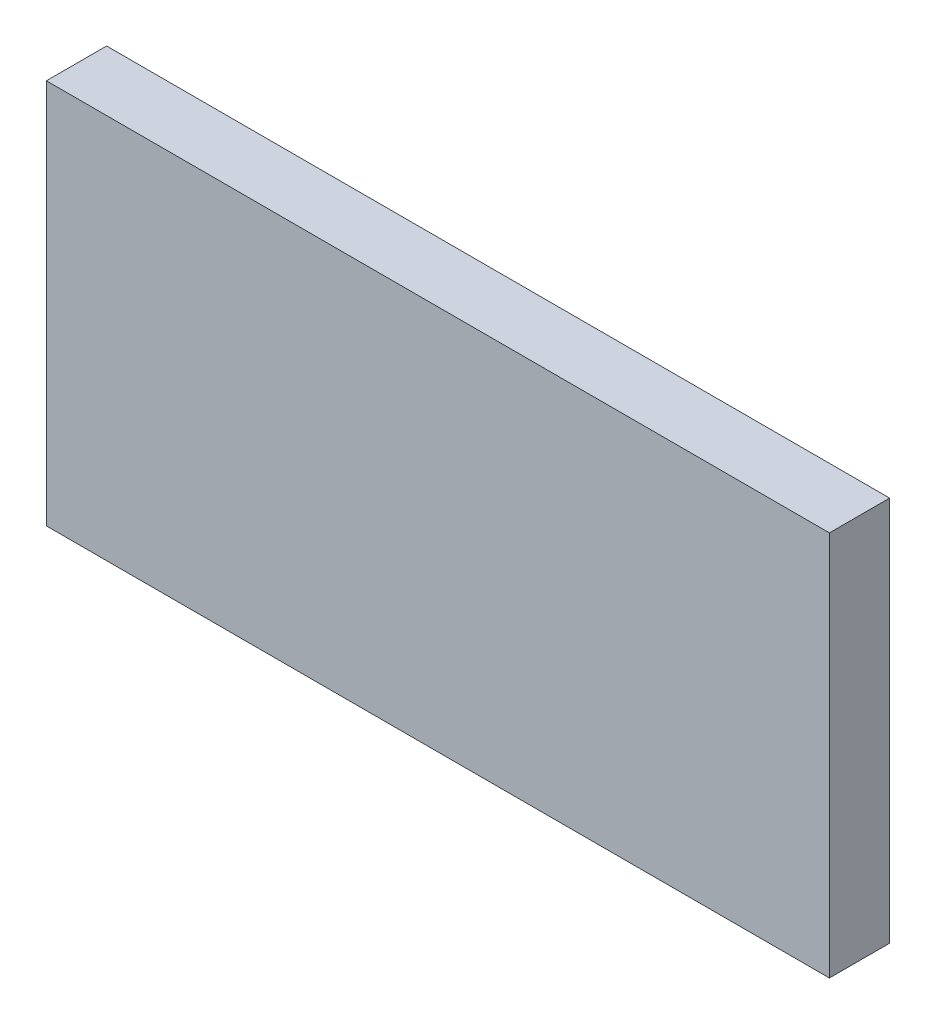
SolidWorks part; units mm, degrees
ref_plane "Front Plane" through (0, 0, 0) normal (0, 0, 1) x (1, 0, 0)
ref_plane "Top Plane" through (0, 0, 0) normal (0, 1, 0) x (1, 0, 0)
ref_plane "Right Plane" through (0, 0, 0) normal (1, 0, 0) x (0, 0, -1)
sketch "Sketch1" plane through (0, 0, 0) normal (0, 0, 1) x (1, 0, 0)
  line L1 (-7.5, 10) -> (7.5, 10)
  line L2 (-7.5, 10) -> (-7.5, -10)
  line L3 (-7.5, -10) -> (7.5, -10)
  line L4 (7.5, 10) -> (7.5, -10)
  line L5 (-7.5, 10) -> (7.5, -10) construction
  line L6 (-7.5, -10) -> (7.5, 10) construction
  point P0 (0, 0)
  dimension "D1" = 15
  dimension "D2" = 20
extrude "Boss-Extrude1" add sketch "Sketch1" along normal blind 230
sketch "Sketch2" plane through (0, 0, 0) normal (0, 0, -1) x (-1, 0, 0)
  line L1 (-32.5, 10) -> (32.5, 10)
  line L2 (-32.5, 10) -> (-32.5, 42)
  line L3 (-32.5, 42) -> (32.5, 42)
  line L4 (32.5, 10) -> (32.5, 42)
  line L6 (-7.5, 10) -> (7.5, 10) construction
  point P4 (0, 10)
  point P10 (0, 10)
  dimension "D1" = 65
  dimension "D2" = 32
extrude "Boss-Extrude6" add sketch "Sketch2" against normal blind 5 separate body
sketch "Sketch7" plane through (32.5, 0, 0) normal (1, 0, 0) x (0, 0, -1)
  line L0 (0, 42) -> (0, 10) construction
  line L1 (0, 33.5) -> (-75, 33.5)
  line L2 (0, 33.5) -> (0, 18.5)
  line L3 (0, 18.5) -> (-75, 18.5)
  line L4 (-75, 33.5) -> (-75, 18.5)
  point P4 (0, 26)
  point P7 (0, 26)
  dimension "D1" = 15
  dimension "D2" = 75
extrude "Boss-Extrude7" add sketch "Sketch7" along normal blind 5 separate body
sketch "Sketch8" plane through (-32.5, 0, 0) normal (-1, 0, 0) x (0, 0, 1)
  line L1 (0, 37.5) -> (75, 37.5)
  line L2 (0, 37.5) -> (0, 18.5)
  line L3 (0, 18.5) -> (75, 18.5)
  line L4 (75, 37.5) -> (75, 18.5)
extrude "Boss-Extrude8" add sketch "Sketch8" along normal blind 5 separate body
sketch "Sketch9" plane through (0, 0, 75) normal (0, 0, 1) x (1, 0, 0)
  line L1 (-32.5, 42) -> (32.5, 42)
  line L2 (-32.5, 42) -> (-32.5, 10)
  line L3 (-32.5, 10) -> (32.5, 10)
  line L4 (32.5, 42) -> (32.5, 10)
extrude "Boss-Extrude11" add sketch "Sketch9" against normal blind 5 separate body
sketch "Sketch10" plane through (-7.5, 0, 0) normal (-1, 0, 0) x (0, 0, 1)
  line L0 (230, 10) -> (230, -10) construction
  line L2 (209.8431, 2) -> (211.3431, 2)
  line L3 (209.8431, 2) -> (209.8431, -2)
  line L4 (209.8431, -2) -> (211.3431, -2)
  line L6 (209.8431, 2) -> (211, 0) construction
  line L7 (209.8431, -2) -> (211, 0) construction
  arc A0 (211.3431, -2) -> (211.3431, 2) centre (217, 0) ccw
  point P4 (230, 0)
  point P5 (211, 0)
  point P11 (209.8431, 0)
  dimension "D1" = 12
  dimension "D2" = 13
  dimension "D3" = 1.5
  dimension "D4" = 4
extrude "Cut-Extrude1" cut sketch "Sketch10" against normal through all
delete or keep bodies "Body-Delete/Keep 2" type delete bodies bodies 108 109 110 107
